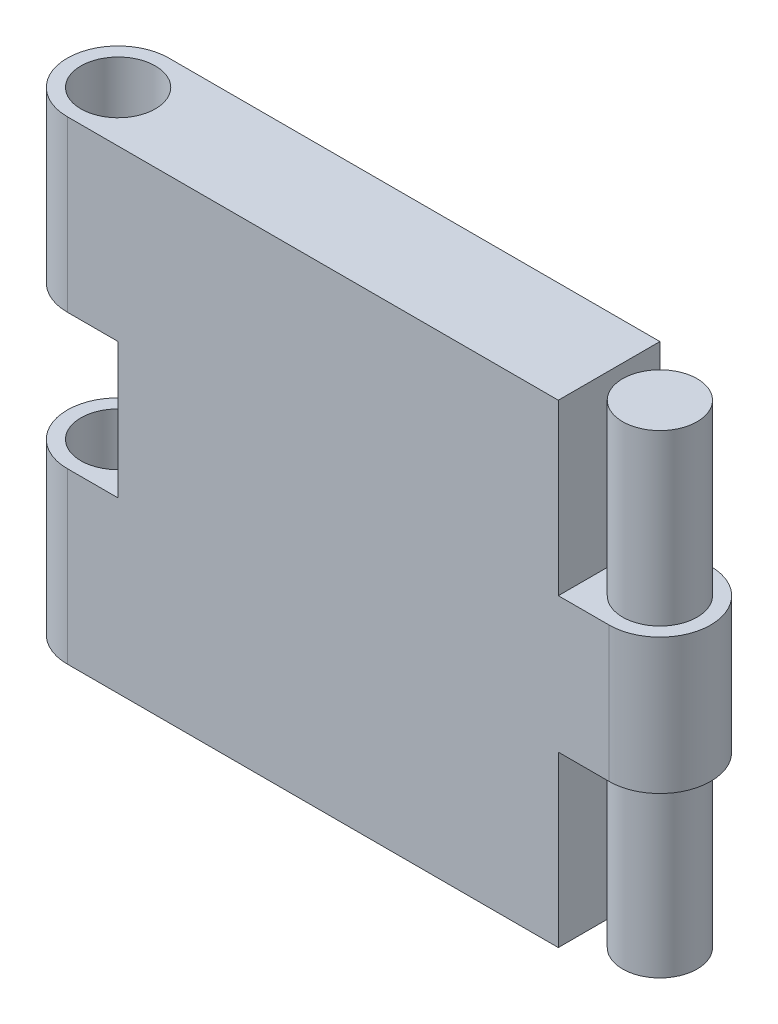
SolidWorks part; units mm, degrees
ref_plane "Front Plane" through (0, 0, 0) normal (0, 0, 1) x (1, 0, 0)
ref_plane "Top Plane" through (0, 0, 0) normal (0, 1, 0) x (1, 0, 0)
ref_plane "Right Plane" through (0, 0, 0) normal (1, 0, 0) x (0, 0, -1)
sketch "Plate Sketch" plane through (0, 0, 0) normal (0, 0, 1) x (1, 0, 0)
  line L1 (-40, 35) -> (40, 35)
  line L2 (-40, 35) -> (-40, -35)
  line L3 (-40, -35) -> (40, -35)
  line L4 (40, 35) -> (40, -35)
  line L5 (-40, 35) -> (40, -35) construction
  line L6 (-40, -35) -> (40, 35) construction
  point P0 (0, 0)
  dimension "D1" = 70
  dimension "D2" = 80
extrude "Plate Extrude" add sketch "Plate Sketch" against normal blind 15
sketch "Hole Sketch" plane through (0, 0, 0) normal (0, 1, 0) x (1, 0, 0)
  line L0 (-32.5, 15) -> (-32.5, 0) construction
  line L1 (40, 15) -> (-40, 15) construction
  line L2 (40, 0) -> (-40, 0) construction
  line L3 (-38, 7.5) -> (-40, 7.5) construction
  line L4 (-40, 15) -> (-40, 0) construction
  circle A0 centre (-32.5, 7.5) radius 5.5
  point P5 (-32.5, 7.5)
  dimension "D1" = 11
  dimension "D2" = 2
extrude "Hole Cut" cut sketch "Hole Sketch" along normal up to surface and the other way up to surface up to face at (0, 35, -7.5) other way up to face at (0, -35, -7.5)
fillet "Female Fillet" 2 edges at (-40, 0, 0) (-40, 0, -15) type full round first side face at (0, 0, 0) second side face at (0, 0, -15) middle face at (-40, 0, -7.5)
sketch "Gap Sketch" plane through (0, 0, 0) normal (0, 1, 0) x (1, 0, 0)
  line L0 (40, 15) -> (-32.5, 15) construction
  line L1 (-40, 15) -> (-25, 15)
  line L2 (-40, 15) -> (-40, 0)
  line L3 (-40, 0) -> (-25, 0)
  line L4 (-25, 15) -> (-25, 0)
  line L5 (-40, 15) -> (-25, 0) construction
  line L6 (-40, 0) -> (-25, 15) construction
  line L7 (40, 0) -> (-32.5, 0) construction
  line L8 (-27, 7.5) -> (-25, 7.5) construction
  arc A0 (-32.5, 15) -> (-32.5, 0) centre (-32.5, 7.5) ccw construction
  circle A1 centre (-32.5, 7.5) radius 5.5 construction
  point P0 (-32.5, 7.5)
  dimension "D1" = 2
extrude "Gap Cut" cut sketch "Gap Sketch" against normal blind 10 and the other way blind 10
sketch "Pin Support Sketch" plane through (0, 0, 0) normal (0, 1, 0) x (1, 0, 0)
  line L0 (40, 15) -> (-32.5, 15) construction
  line L1 (40, 15) -> (55, 15)
  line L2 (40, 15) -> (40, 0)
  line L3 (40, 0) -> (55, 0)
  line L4 (55, 15) -> (55, 0)
  line L5 (40, 15) -> (55, 0) construction
  line L6 (40, 0) -> (55, 15) construction
  line L7 (40, 0) -> (-32.5, 0) construction
  line L8 (40, 15) -> (40, 0) construction
  point P0 (47.5, 7.5)
extrude "Pin Support Extrude" add sketch "Pin Support Sketch" along normal blind 10 and the other way blind 10
sketch "Pin Sketch" plane through (0, 10, 0) normal (0, 1, 0) x (1, 0, 0)
  circle A0 centre (47.5, 7.5) radius 5.5
  point P3 (47.5, 7.5)
  dimension "D1" = 11
extrude "Pin Extrude" add sketch "Pin Sketch" along normal up to surface and the other way up to surface up to face at (-32.5, 35, -2) other way up to face at (-32.5, -35, -13)
fillet "Male Fillet" 2 edges at (55, 0, -15) (55, 0, 0) type full round first side face at (7.5, 0, -15) second side face at (7.5, 0, 0) middle face at (55, 0, -7.5)
